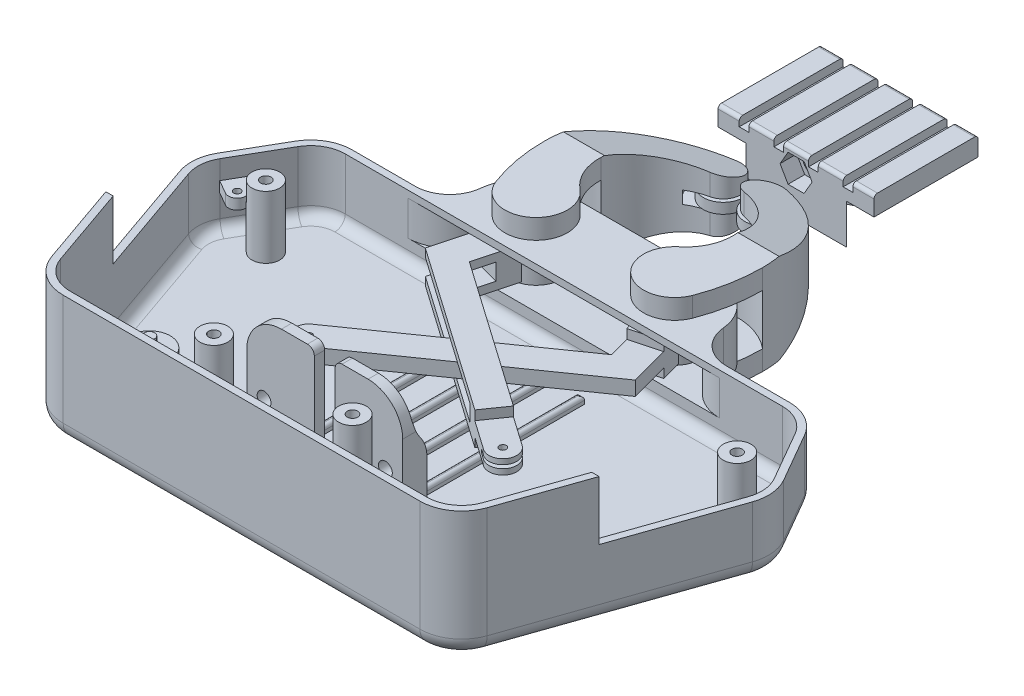
SolidWorks part; units mm, degrees
ref_plane "Front Plane" through (0, 0, 0) normal (0, 0, 1) x (1, 0, 0)
ref_plane "Top Plane" through (0, 0, 0) normal (0, 1, 0) x (1, 0, 0)
ref_plane "Right Plane" through (0, 0, 0) normal (1, 0, 0) x (0, 0, -1)
sketch "Sketch1" plane through (0, 0, 0) normal (0, 1, 0) x (1, 0, 0)
  line L0 (-70, -55) -> (-35, -55)
  line L1 (70, -55) -> (84.4338, -80)
  line L2 (84.4338, -80) -> (60, -150)
  line L3 (60, -150) -> (-60, -150)
  line L4 (-60, -150) -> (-84.4338, -80)
  line L5 (-84.4338, -80) -> (-70, -55)
  line L6 (-35, -55) -> (-35, -35)
  line L7 (-35, -35) -> (35, -35)
  line L8 (35, -35) -> (35, -55)
  line L9 (0, -55) -> (0, -122.8119) construction
  line L10 (35, -55) -> (70, -55)
  point P15 (0, -150)
  dimension "D1" = 25
  dimension "D2" = 140
  dimension "D3" = 70
  dimension "D4" = 120
  dimension "D5" = 70
  dimension "D6" = 55
  dimension "D7" = 120
  dimension "D8" = 20
  dimension "D9" = 70
  dimension "D10" = 35
extrude "Boss-Extrude1" add sketch "Sketch1" along normal blind 2
sketch "Sketch2" plane through (0, 2, 0) normal (0, 1, 0) x (1, 0, 0)
  line L0 (84.4338, -80) -> (70, -55) construction
  line L1 (60, -150) -> (84.4338, -80) construction
  line L2 (-60, -150) -> (60, -150) construction
  line L3 (-84.4338, -80) -> (-60, -150) construction
  line L4 (-70, -55) -> (-84.4338, -80) construction
  line L6 (84.4338, -80) -> (70, -55)
  line L7 (60, -150) -> (84.4338, -80)
  line L8 (-60, -150) -> (60, -150)
  line L9 (-84.4338, -80) -> (-60, -150)
  line L10 (-70, -55) -> (-84.4338, -80)
  line L11 (70, -55) -> (35, -55)
  line L12 (68.8453, -57) -> (33, -57)
  line L13 (-68.8453, -57) -> (-82.2434, -80.2062)
  line L14 (-82.2434, -80.2062) -> (-58.5798, -148)
  line L15 (-58.5798, -148) -> (58.5798, -148)
  line L16 (58.5798, -148) -> (82.2434, -80.2062)
  line L17 (82.2434, -80.2062) -> (68.8453, -57)
  line L18 (-35, -55) -> (-35, -35)
  line L19 (-35, -35) -> (35, -35)
  line L20 (35, -35) -> (35, -55)
  line L21 (-35, -55) -> (-70, -55)
  line L22 (-33, -57) -> (-33, -37)
  line L23 (70, -55) -> (-70, -55) construction
  line L24 (-33, -37) -> (33, -37)
  line L25 (33, -37) -> (33, -57)
  line L26 (-33, -57) -> (-68.8453, -57)
  line L28 (68.8453, -57) -> (-68.8453, -57) construction
  dimension "D1" = 2
  dimension "D2" = 2
  dimension "D3" = 2
  dimension "D4" = 2
extrude "Boss-Extrude2" add sketch "Sketch2" along normal blind 35
sketch "Sketch20" plane through (0, 0, 0) normal (0, -1, 0) x (1, 0, 0)
  line L0 (70, 55) -> (35, 55) construction
  line L1 (-35, 35) -> (35, 35)
  line L2 (-35, 35) -> (-35, 55)
  line L3 (-35, 55) -> (35, 55)
  line L4 (35, 35) -> (35, 55)
  line L5 (35, 55) -> (35, 35) construction
  line L6 (35, 35) -> (-35, 35) construction
  line L7 (-35, 35) -> (-35, 55) construction
extrude "Cut-Extrude7" cut sketch "Sketch20" against normal blind 8
sketch "Sketch21" plane through (0, 8, 0) normal (0, -1, 0) x (1, 0, 0)
  line L1 (-35, 35) -> (35, 35)
  line L2 (-35, 35) -> (-35, 55)
  line L3 (-35, 55) -> (35, 55)
  line L4 (35, 35) -> (35, 55)
extrude "Boss-Extrude12" add sketch "Sketch21" along normal blind 2
sketch "Sketch22" plane through (0, 0, 55) normal (0, 0, 1) x (1, 0, 0)
  line L1 (-33, 2) -> (33, 2)
  line L2 (-33, 2) -> (-33, 8)
  line L3 (-33, 8) -> (33, 8)
  line L4 (33, 2) -> (33, 8)
extrude "Boss-Extrude13" add sketch "Sketch22" along normal blind 2
sketch "Sketch23" plane through (0, 37, 0) normal (0, 1, 0) x (1, 0, 0)
  line L0 (35, -35) -> (-35, -35) construction
  line L1 (-35, -57) -> (35, -57)
  line L2 (-35, -57) -> (-35, -35)
  line L3 (-35, -35) -> (35, -35)
  line L4 (35, -57) -> (35, -35)
  line L5 (-35, -35) -> (-35, -55) construction
  line L6 (35, -55) -> (35, -35) construction
  line L7 (33, -57) -> (-33, -57) construction
extrude "Cut-Extrude8" cut sketch "Sketch23" against normal offset from surface (19 mm away) 12 up to face at (0, 6, 45)
sketch "Sketch24" plane through (0, 18, 0) normal (0, 1, 0) x (1, 0, 0)
  line L1 (-35, -35) -> (35, -35)
  line L2 (-35, -35) -> (-35, -57)
  line L3 (-35, -57) -> (35, -57)
  line L4 (35, -35) -> (35, -57)
  line L5 (-35, -35) -> (35, -35) construction
  line L6 (-35, -55) -> (-35, -35) construction
  line L8 (35, -35) -> (35, -55) construction
  line L9 (-35, -57) -> (-68.8453, -57) construction
extrude "Boss-Extrude16" add sketch "Sketch24" along normal blind 2
sketch "Sketch26" plane through (0, 0, 0) normal (0, -1, 0) x (1, 0, 0)
  line L0 (0, 35) -> (0, 168.1743) construction
  line L1 (-35, 35) -> (35, 35) construction
  circle A0 centre (20, 45) radius 7.5
  circle A1 centre (-20, 45) radius 7.5
  dimension "D1" = 15
  dimension "D2" = 10
  dimension "D3" = 20
extrude "Cut-Extrude9" cut sketch "Sketch26" against normal through all
sketch "Sketch27" plane through (0, 8, 0) normal (0, 1, 0) x (1, 0, 0)
  line L0 (-29.5, -45) -> (-27.5, -45)
  line L1 (-10.5, -45) -> (-12.5, -45)
  line L2 (0, -35) -> (0, -72.4721) construction
  line L3 (35, -35) -> (-35, -35) construction
  line L4 (29.5, -45) -> (27.5, -45)
  line L5 (10.5, -45) -> (12.5, -45)
  arc A0 (-27.5, -45) -> (-12.5, -45) centre (-20, -45) cw
  circle A1 centre (-20, -45) radius 7.5 construction
  arc A2 (-10.5, -45) -> (-29.5, -45) centre (-20, -45) ccw
  arc A3 (27.5, -45) -> (12.5, -45) centre (20, -45) ccw
  arc A4 (10.5, -45) -> (29.5, -45) centre (20, -45) cw
  dimension "D1" = 9.5
extrude "Boss-Extrude18" add sketch "Sketch27" along normal up to surface (10 mm away) up to face at (20, 18, 52.5)
sketch "Sketch25" plane through (0, 20, 0) normal (0, 1, 0) x (1, 0, 0)
  line L0 (35, -57) -> (35, -55) construction
  line L1 (-35, -57) -> (35, -57)
  line L2 (-35, -57) -> (-35, -55)
  line L3 (-35, -55) -> (35, -55)
  line L4 (35, -57) -> (35, -55)
  line L5 (-35, -57) -> (35, -57) construction
  line L6 (-35, -55) -> (-35, -57) construction
  line L7 (-35, -55) -> (-70, -55) construction
extrude "Boss-Extrude17" add sketch "Sketch25" along normal up to surface (17 mm away) up to face at (0, 37, 85.2758)
fillet "Fillet8" radius 10 2 edges at (-33, 13, 37) (33, 13, 37)
fillet "Fillet9" radius 12 2 edges at (35, 13, 35) (-35, 13, 35)
sketch "Sketch32" plane through (0, 6, 0) normal (0, -1, 0) x (1, 0, 0)
  circle A0 centre (-20, 45) radius 7.35
  circle A1 centre (-20, 45) radius 7.5 construction
  dimension "D1" = 14.7
extrude "Boss-Extrude22" add sketch "Sketch32" against normal offset from surface (14.6 mm away) 0.3 from offset 0.3 separate body up to face at (0, 20, 44.8382) offset beyond the face yes
ref_plane "Plane6" through (0, 13, 0) normal (0, -1, 0) x (-1, 0, 0)
sketch "Sketch34" plane through (0, 13, 0) normal (0, -1, 0) x (-1, 0, 0)
  line L0 (0, -55) -> (0, -6.1056) construction
  line L1 (-35, -55) -> (35, -55) construction
  circle A0 centre (6, -5) radius 6
  circle A1 centre (20, -45) radius 7.5 construction
  circle A2 centre (20, -45) radius 7.5 construction
  circle A3 centre (6, -5) radius 2.8
  dimension "D1" = 12
  dimension "D3" = 5.6
  dimension "D2" = 40
extrude "Boss-Extrude23" add sketch "Sketch34" along normal mid plane 3 separate body
sketch "Sketch36" plane through (0, 13, 0) normal (0, -1, 0) x (-1, 0, 0)
  circle A0 centre (6, -5) radius 2.5
  dimension "D1" = 5
extrude "Boss-Extrude24" add sketch "Sketch36" along normal mid plane 3.6 separate body
sketch "Sketch37" plane through (0, 11.2, 0) normal (0, -1, 0) x (1, 0, 0)
  line L0 (-1.0405, 27.7489) -> (-20, 45) construction
  line L1 (-6, 5) -> (-1.0405, 27.7489) construction
  line L2 (0.4875, 31.2396) -> (-20, 45) construction
  line L3 (0.4875, 31.2396) -> (-6, 5) construction
  arc A0 (-4.935, 9.8853) -> (-7.2001, 0.1462) centre (-6, 5) cw
  circle A1 centre (-20, 45) radius 7.35 construction
  arc A2 (-14.5636, 40.0535) -> (-26.1015, 49.0981) centre (-20, 45) ccw construction
  arc A3 (-4.935, 9.8853) -> (-14.5636, 40.0535) centre (-1.0405, 27.7489) cw construction
  arc A4 (-26.1015, 49.0981) -> (-7.2001, 0.1462) centre (0.4875, 31.2396) ccw construction
  arc A5 (-31.5421, 31.1877) -> (-19.3089, 27.0133) centre (-20, 45) ccw
  arc A6 (-31.5421, 31.1877) -> (-7.2001, 0.1462) centre (0.4875, 31.2396) ccw
  arc A7 (-19.3089, 27.0133) -> (-4.935, 9.8853) centre (-1.0405, 27.7489) ccw
  dimension "D1" = 5
  dimension "D4" = 18
  dimension "D2" = 60
  dimension "D3" = 70
extrude "Boss-Extrude25" add sketch "Sketch37" along normal up to surface (11.2 mm away) up to face at (0, 0, 95)
sketch "Sketch39" plane through (0, 5.7, 0) normal (0, -1, 0) x (1, 0, 0)
  arc A0 (-14.3353, 38.0064) -> (-28.4038, 48.2211) centre (-20, 45) ccw
  arc A1 (-31.5421, 31.1877) -> (-19.3089, 27.0133) centre (-20, 45) ccw construction
  arc A2 (-31.5421, 31.1877) -> (-19.3089, 27.0133) centre (-20, 45) ccw
  arc A3 (-31.5421, 31.1877) -> (-28.4038, 48.2211) centre (15.8356, 31.2644) cw
  arc A4 (-31.5421, 31.1877) -> (-7.2001, 0.1462) centre (0.4875, 31.2396) ccw construction
  arc A5 (-19.3089, 27.0133) -> (-14.3353, 38.0064) centre (-5.8694, 27.5545) cw
  arc A6 (-19.3089, 27.0133) -> (-4.935, 9.8853) centre (-1.0405, 27.7489) ccw construction
  dimension "D1" = 18
extrude "Boss-Extrude26" add sketch "Sketch39" along direction (0, -1, 0) on the side of the normal up to surface (5.7 mm away) up to face at (-16.6764, 0, 14.8256)
sketch "Sketch40" plane through (0, 20.3, 0) normal (0, 1, 0) x (1, 0, 0)
  arc A1 (-28.4038, -48.2211) -> (-14.3353, -38.0064) centre (-20, -45) ccw construction
  arc A2 (-19.3089, -27.0133) -> (-14.3353, -38.0064) centre (-5.8694, -27.5545) ccw construction
  arc A3 (-19.3089, -27.0133) -> (-31.5421, -31.1877) centre (-20, -45) ccw construction
  arc A4 (-31.5421, -31.1877) -> (-28.4038, -48.2211) centre (15.8356, -31.2644) ccw construction
  arc A5 (-28.4038, -48.2211) -> (-14.3353, -38.0064) centre (-20, -45) ccw
  arc A6 (-19.3089, -27.0133) -> (-14.3353, -38.0064) centre (-5.8694, -27.5545) ccw
  arc A7 (-19.3089, -27.0133) -> (-31.5421, -31.1877) centre (-20, -45) ccw
  arc A8 (-31.5421, -31.1877) -> (-28.4038, -48.2211) centre (15.8356, -31.2644) ccw
extrude "Boss-Extrude27" add sketch "Sketch40" along normal blind 5.7
sketch "Sketch41" plane through (0, 14.8, 0) normal (0, 1, 0) x (1, 0, 0)
  arc A0 (-4.935, -9.8853) -> (-7.2001, -0.1462) centre (-6, -5) ccw construction
  arc A1 (-19.3089, -27.0133) -> (-31.5421, -31.1877) centre (-20, -45) ccw construction
  arc A2 (-4.935, -9.8853) -> (-19.3089, -27.0133) centre (-1.0405, -27.7489) ccw construction
  arc A3 (-7.2001, -0.1462) -> (-31.5421, -31.1877) centre (0.4875, -31.2396) ccw construction
  arc A4 (-4.935, -9.8853) -> (-7.2001, -0.1462) centre (-6, -5) ccw
  arc A5 (-19.3089, -27.0133) -> (-31.5421, -31.1877) centre (-20, -45) ccw
  arc A6 (-4.935, -9.8853) -> (-19.3089, -27.0133) centre (-1.0405, -27.7489) ccw
  arc A7 (-7.2001, -0.1462) -> (-31.5421, -31.1877) centre (0.4875, -31.2396) ccw
extrude "Boss-Extrude28" add sketch "Sketch41" along normal up to surface (11.2 mm away) up to face at (-22.3518, 26, 38.2988)
sketch "Sketch43" plane through (0, 11.2, 0) normal (0, 1, 0) x (1, 0, 0)
  arc A1 (-4.935, -9.8853) -> (-19.3089, -27.0133) centre (-1.0405, -27.7489) ccw construction
  arc A3 (-19.3089, -27.0133) -> (-31.5421, -31.1877) centre (-20, -45) ccw construction
  arc A5 (-10.5871, -12.156) -> (-19.3089, -27.0133) centre (-1.0405, -27.7489) ccw
  arc A6 (-7.2001, -0.1462) -> (-31.5421, -31.1877) centre (0.4875, -31.2396) ccw construction
  arc A7 (-19.3089, -27.0133) -> (-31.5421, -31.1877) centre (-20, -45) ccw
  arc A8 (-14.2045, -2.7783) -> (-10.5871, -12.156) centre (-6, -5) ccw
  arc A9 (-14.2045, -2.7783) -> (-31.5421, -31.1877) centre (0.4875, -31.2396) ccw
  arc A13 (-4.935, -9.8853) -> (-7.2001, -0.1462) centre (-6, -5) ccw construction
  dimension "D1" = 17
extrude "Boss-Extrude29" add sketch "Sketch43" along normal up to surface (3.6 mm away) up to face at (-6, 14.8, 2.5)
sketch "Sketch44" plane through (0, 0, 0) normal (1, 0, 0) x (0, 0, -1)
  line L0 (0, 17.8) -> (-26.0133, 26)
  line L1 (-26.0133, 26) -> (0, 26)
  line L4 (0, 14.8) -> (0, 26) construction
  line L5 (-9.8853, 26) -> (-27.0133, 26) construction
  line L6 (0, 17.8) -> (0, 26)
  line L7 (-15.422, 13) -> (22.0298, 13) construction
  line L8 (-94.4278, 13) -> (94.4278, 13) construction
  line L9 (0, 8.2) -> (-26.0133, 0)
  line L10 (-26.0133, 0) -> (0, 0)
  line L11 (0, 8.2) -> (0, 0)
  dimension "D1" = 1
  dimension "D2" = 3
extrude "Cut-Extrude10" cut sketch "Sketch44" against normal up to surface (31.1129 mm away) up to face at (-19.4224, 13, 12.2098)
ref_plane "Plane2" through (0, 0, 0) normal (1, 0, 0) x (0, 0, -1)
ref_plane "Plane3" through (0, 0, 126) normal (0, 0, -1) x (-1, 0, 0)
sketch "Sketch45" plane through (0, 13, 0) normal (0, -1, 0) x (-1, 0, 0)
  circle A0 centre (6, -5) radius 6 construction
  circle A1 centre (6, -5) radius 6
  circle A2 centre (6, -5) radius 5.75
  dimension "D1" = 11.5
extrude "Cut-Extrude11" cut sketch "Sketch45" along normal up to surface (1.5 mm away) from surface up to face at (-6, 11.5, -1) starting at face at (-6, 14.5, -1)
mirror "Mirror8" about plane through (0, 0, 0) normal (1, 0, 0) of bodies 137 140
sketch "Sketch8" plane through (0, 0, 126) normal (0, 0, -1) x (-1, 0, 0)
  line L0 (-68.8453, 2) -> (68.8453, 2) construction
  line L1 (-68.8453, 2) -> (68.8453, 2) construction
  line L2 (60, 0) -> (-60, 0) construction
  line L3 (22.5, 2) -> (-22.5, 2)
  line L4 (22.5, 2) -> (22.5, 36)
  line L5 (22.5, 36) -> (-22.5, 36)
  line L6 (-22.5, 2) -> (-22.5, 36)
  line L7 (60, 0) -> (-60, 0) construction
  line L8 (0, 14.8493) -> (0, -14.8493) construction
  dimension "D1" = 34
  dimension "D2" = 45
  dimension "D3" = 22.5
extrude "Boss-Extrude5" add sketch "Sketch8" along normal blind 3
sketch "Sketch9" plane through (0, 2, 0) normal (0, 1, 0) x (1, 0, 0)
  line L1 (-22.5, -123) -> (-19.5, -123)
  line L2 (-22.5, -123) -> (-22.5, -119)
  line L3 (-22.5, -119) -> (-19.5, -119)
  line L4 (-19.5, -123) -> (-19.5, -119)
  line L5 (22.5, -123) -> (19.5, -123)
  line L6 (22.5, -123) -> (22.5, -119)
  line L7 (22.5, -119) -> (19.5, -119)
  line L8 (19.5, -123) -> (19.5, -119)
  dimension "D1" = 3
  dimension "D2" = 4
extrude "Boss-Extrude6" add sketch "Sketch9" along normal blind 20
fillet "Fillet1" radius 10 2 edges at (-21, 22, 123) (21, 22, 123)
fillet "Fillet2" radius 10 2 edges at (-21, 22, 119) (21, 22, 119)
sketch "Sketch11" plane through (0, 2, 0) normal (0, 1, 0) x (1, 0, 0)
  line L0 (-58.5798, -148) -> (58.5798, -148) construction
  circle A0 centre (-43.5798, -133) radius 3.5
  circle A1 centre (-43.5798, -133) radius 1.85
  dimension "D1" = 7
  dimension "D4" = 3.7
  dimension "D2" = 15
  dimension "D3" = 15
sketch "Sketch15" plane through (0, 0, 126) normal (0, 0, 1) x (1, 0, 0)
  line L1 (22.5, 2) -> (-22.5, 2) construction
  line L2 (22.5, 2) -> (-22.5, 2) construction
  line L3 (0, -14.8493) -> (0, 14.8493) construction
  circle A0 centre (17.5, 16) radius 2
  circle A1 centre (-17.5, 16) radius 2
  circle A3 centre (0, 8) radius 4.65
  dimension "D1" = 8
  dimension "D2" = 4
  dimension "D3" = 4
  dimension "D6" = 9.3
  dimension "D4" = 35
  dimension "D5" = 17.5
  dimension "D7" = 6
extrude "Cut-Extrude5" cut sketch "Sketch15" against normal up to surface (3 mm away) up to face at (0, 24.5, 123)
fillet "Fillet3" radius 10 8 edges at (-35, 13, 55) (35, 13, 55) (58.5798, 19.5, 148) (-58.5798, 19.5, 148) (82.2434, 19.5, 80.2062) (68.8453, 19.5, 57) (-82.2434, 19.5, 80.2062) (-68.8453, 19.5, 57)
fillet "Fillet4" radius 12 8 edges at (-60, 18.5, 150) (-84.4338, 18.5, 80) (-70, 18.5, 55) (-33, 13, 57) (33, 13, 57) (70, 18.5, 55) (60, 18.5, 150) (84.4338, 18.5, 80)
fillet "Fillet5" radius 10 2 edges at (22.5, 36, 124.5) (-22.5, 36, 124.5)
fillet "Fillet6" radius 3 12 edges at (-70.8266, 2, 112.9143) (-81.2478, 2, 80.3) (-75.842, 2, 69.1187) (-68.0718, 2, 58.3397) (0, 2, 57) (68.0718, 2, 58.3397) (75.842, 2, 69.1187) (81.2478, 2, 80.3) (70.8266, 2, 112.9143) (0, 2, 148) (-57.2685, 2, 146.1534) (57.2685, 2, 146.1534)
fillet "Fillet7" radius 5 12 edges at (69.0718, 0, 56.6077) (77.5741, 0, 68.1187) (83.2389, 0, 80.1125) (72.7148, 0, 113.5734) (58.4264, 0, 147.7841) (0, 0, 150) (-58.4264, 0, 147.7841) (-72.7148, 0, 113.5734) (-83.2389, 0, 80.1125) (-77.5741, 0, 68.1187) (-69.0718, 0, 56.6077) (0, 0, 55)
sketch "Sketch16" plane through (0, 0, 0) normal (1, 0, 0) x (0, 0, -1)
  line L0 (-83.5443, 0) -> (-140.3069, 0) construction
  line L1 (-118, 40) -> (-28, 40)
  line L2 (-118, 40) -> (-118, 20)
  line L3 (-118, 20) -> (-28, 20)
  line L4 (-28, 40) -> (-28, 20)
  line L5 (-150, 5) -> (-150, 37) construction
  dimension "D1" = 20
  dimension "D2" = 32
  dimension "D3" = 20
  dimension "D4" = 90
extrude "Cut-Extrude6" cut sketch "Sketch16" against normal through all both and the other way through all
sketch "Sketch17" plane through (0, 2, 0) normal (0, 1, 0) x (1, 0, 0)
  line L0 (0, -14.8493) -> (0, 14.8493) construction
  line L4 (-63.0718, -55) -> (-44.9089, -55) construction
  circle A2 centre (-68, -75) radius 4
  circle A4 centre (-68, -75) radius 1.5
  circle A10 centre (68, -75) radius 1.5
  circle A11 centre (68, -75) radius 4
  dimension "D7" = 8
  dimension "D9" = 3
  dimension "D4" = 20
  dimension "D5" = 68
extrude "Boss-Extrude10" add sketch "Sketch17" along normal up to surface (18 mm away) up to face at (0, 20, 71.1525)
sketch "Sketch19" plane through (0, 2, 0) normal (0, 1, 0) x (1, 0, 0)
  line L0 (0, -14.8493) -> (0, 14.8493) construction
  line L1 (-51.4786, -150) -> (51.4786, -150) construction
  circle A0 centre (-20, -138) radius 4
  circle A1 centre (-20, -138) radius 1.5
  circle A2 centre (20, -138) radius 1.5
  circle A3 centre (20, -138) radius 4
  dimension "D1" = 3
  dimension "D2" = 8
  dimension "D3" = 20
  dimension "D4" = 12
extrude "Boss-Extrude11" add sketch "Sketch19" along normal up to surface (35 mm away) up to face at (0, 37, 136.7604)
sketch "Sketch46" plane through (0, 0, 126) normal (0, 0, 1) x (1, 0, 0)
  line L0 (-3, 8) -> (-3, 36)
  line L1 (-3, 36) -> (3, 36)
  line L3 (-3, 8) -> (3, 8)
  line L5 (-12.5, 36) -> (12.5, 36) construction
  line L7 (3, 36) -> (3, 8)
  circle A0 centre (0, 8) radius 4.65 construction
  circle A1 centre (0, 8) radius 4.65 construction
  dimension "D1" = 6
extrude "Cut-Extrude12" cut sketch "Sketch46" against normal up to surface (3 mm away) up to face at (-4.65, 8, 123)
fillet "Fillet10" radius 2 2 edges at (-3, 36, 124.5) (3, 36, 124.5)
sketch "Sketch49" plane through (0, 13, 0) normal (0, -1, 0) x (-1, 0, 0)
  line L0 (20, -45) -> (6, -5) construction
  line L1 (27.0996, -43.0977) -> (32.923, -64.831) construction
  line L2 (30.3078, -66.6622) -> (-25.7197, -105.8931)
  line L3 (12.9004, -46.9023) -> (17.9052, -65.5804) construction
  line L4 (17.9052, -65.5804) -> (-30.3083, -99.3398)
  line L5 (63.0718, -57) -> (-63.0718, -57) construction
  line L6 (30.3078, -66.6622) -> (25.7352, -49.5968)
  line L7 (20.5204, -63.7492) -> (17.3316, -51.8485)
  line L8 (17.9052, -65.5804) -> (20.5204, -63.7492)
  line L9 (30.3078, -66.6622) -> (32.923, -64.831) construction
  circle A0 centre (20, -45) radius 7.35 construction
  arc A1 (17.3316, -51.8485) -> (25.7352, -49.5968) centre (20, -45) ccw
  circle A2 centre (20, -45) radius 75 construction
  arc A3 (7.2001, -0.1462) -> (4.935, -9.8853) centre (6, -5) ccw construction
  arc A4 (7.2001, -0.1462) -> (4.935, -9.8853) centre (6, -5) ccw construction
  arc A5 (-30.3083, -99.3398) -> (-25.7197, -105.8931) centre (-28.014, -102.6165) ccw
  point P15 (26.4546, -40.6906)
  point P19 (0, 0)
  point P20 (27.0996, -43.0977)
  dimension "D1" = 150
  dimension "D2" = 110
  dimension "D3" = 4
  dimension "D4" = 22.5
  dimension "D5" = 35
  dimension "D6" = 3
  dimension "D7" = 3
extrude "Boss-Extrude30" add sketch "Sketch49" along normal offset from surface 0.3 and the other way offset from surface 0.3 separate body up to face at (0, 8, 45.5486) other way up to face at (0, 18, 45.5486)
sketch "Sketch50" plane through (-41.2919, 0, 58.971) normal (-0.5736, 0, 0.8192) x (0.8192, 0, 0.5736)
  line L0 (13.4091, 8.3) -> (13.4091, 17.7) construction
  line L1 (13.4091, 15.4) -> (65.8061, 15.4)
  line L2 (13.4091, 15.4) -> (13.4091, 10.6)
  line L3 (13.4091, 10.6) -> (65.8061, 10.6)
  line L4 (65.8061, 15.4) -> (65.8061, 10.6)
  line L5 (85.8061, 8.3) -> (85.8061, 17.7) construction
  line L6 (13.4091, 15.4) -> (13.4091, 17.7) construction
  line L7 (81.8061, 17.7) -> (13.4091, 17.7) construction
  line L8 (13.4091, 10.6) -> (13.4091, 8.3) construction
  line L9 (13.4091, 8.3) -> (81.8061, 8.3) construction
  dimension "D1" = 4.8
  dimension "D2" = 0
  dimension "D3" = 20
extrude "Cut-Extrude13" cut sketch "Sketch50" against normal up to surface (8 mm away) up to face at (4.894, 13, 81.5445)
sketch "Sketch51" plane through (0, 13, 0) normal (0, -1, 0) x (-1, 0, 0)
  line L0 (30.3078, -66.6622) -> (25.7352, -49.5968) construction
  line L1 (17.3316, -51.8485) -> (20.5204, -63.7492) construction
  line L3 (-25.7197, -105.8931) -> (30.3078, -66.6622) construction
  line L6 (20.5204, -63.7492) -> (-30.3083, -99.3398) construction
  line L22 (17.3316, -51.8485) -> (20.5204, -63.7492) construction
  line L23 (20.5204, -63.7492) -> (-30.3083, -99.3398) construction
  line L24 (-25.7197, -105.8931) -> (30.3078, -66.6622) construction
  line L25 (30.3078, -66.6622) -> (25.7352, -49.5968) construction
  line L26 (0, 14.8493) -> (0, -14.8493) construction
  line L27 (-20.5204, -63.7492) -> (30.3083, -99.3398)
  line L28 (-17.3316, -51.8485) -> (-20.5204, -63.7492)
  line L29 (-30.3078, -66.6622) -> (-25.7352, -49.5968)
  line L30 (25.7197, -105.8931) -> (-30.3078, -66.6622)
  arc A0 (17.3316, -51.8485) -> (25.7352, -49.5968) centre (20, -45) ccw construction
  arc A6 (-30.3083, -99.3398) -> (-25.7197, -105.8931) centre (-28.014, -102.6165) ccw construction
  arc A10 (-30.3083, -99.3398) -> (-25.7197, -105.8931) centre (-28.014, -102.6165) ccw construction
  arc A11 (17.3316, -51.8485) -> (25.7352, -49.5968) centre (20, -45) ccw construction
  arc A12 (30.3083, -99.3398) -> (25.7197, -105.8931) centre (28.014, -102.6165) cw
  arc A13 (-17.3316, -51.8485) -> (-25.7352, -49.5968) centre (-20, -45) cw
extrude "Boss-Extrude32" add sketch "Sketch51" along normal offset from surface 0.3 and the other way offset from surface 0.4 up to face at (-9.3465, 10.6, 75.4798) other way up to face at (-9.3465, 15.4, 75.4798)
sketch "Sketch52" plane through (0, 13, 0) normal (0, -1, 0) x (-1, 0, 0)
  line L2 (-25.7352, -49.5968) -> (-30.3078, -66.6622) construction
  line L3 (-20.5204, -63.7492) -> (-17.3316, -51.8485) construction
  line L6 (-25.7352, -49.5968) -> (-27.3076, -55.4652)
  line L7 (-18.9041, -57.717) -> (-17.3316, -51.8485)
  line L9 (-18.9041, -57.717) -> (-27.3076, -55.4652)
  line L10 (63.0718, -57) -> (-63.0718, -57) construction
  arc A0 (-25.7352, -49.5968) -> (-17.3316, -51.8485) centre (-20, -45) ccw construction
  arc A1 (-25.7352, -49.5968) -> (-17.3316, -51.8485) centre (-20, -45) ccw
  circle A2 centre (-20, -45) radius 12 construction
  point P2 (-27.4936, -56.1593)
extrude "Boss-Extrude33" add sketch "Sketch52" along normal up to surface (4.7 mm away) from surface up to face at (-5.8265, 8.3, 73.4601) starting at face at (-5.8265, 17.7, 73.4601)
sketch "Sketch53" plane through (0, 17.7, 0) normal (0, 1, 0) x (1, 0, 0)
  line L0 (-20.5204, -63.7492) -> (30.3083, -99.3398) construction
  line L1 (25.7197, -105.8931) -> (-30.3078, -66.6622) construction
  line L2 (21.8792, -93.4377) -> (30.3083, -99.3398)
  line L3 (25.7197, -105.8931) -> (17.2906, -99.9909)
  line L4 (17.2906, -99.9909) -> (21.8792, -93.4377)
  arc A0 (25.7197, -105.8931) -> (30.3083, -99.3398) centre (28.014, -102.6165) ccw construction
  arc A1 (25.7197, -105.8931) -> (30.3083, -99.3398) centre (28.014, -102.6165) ccw
  point P5 (31.2906, -104.9108)
  dimension "D1" = 14
extrude "Cut-Extrude14" cut sketch "Sketch53" against normal up to surface (2.7 mm away) up to face at (6.2892, 15, 75.1868)
sketch "Sketch54" plane through (0, 8.3, 0) normal (0, -1, 0) x (1, 0, 0)
  line L0 (25.7197, 105.8931) -> (17.2906, 99.9909) construction
  line L1 (21.8792, 93.4377) -> (30.3083, 99.3398) construction
  line L2 (17.2906, 99.9909) -> (21.8792, 93.4377) construction
  line L3 (25.7197, 105.8931) -> (17.2906, 99.9909)
  line L4 (21.8792, 93.4377) -> (30.3083, 99.3398)
  line L5 (17.2906, 99.9909) -> (21.8792, 93.4377)
  arc A0 (30.3083, 99.3398) -> (25.7197, 105.8931) centre (28.014, 102.6165) ccw construction
  arc A1 (30.3083, 99.3398) -> (25.7197, 105.8931) centre (28.014, 102.6165) ccw
extrude "Cut-Extrude15" cut sketch "Sketch54" against normal up to surface (2.6 mm away) up to face at (6.2892, 10.9, 75.1868)
sketch "Sketch55" plane through (0, 15, 0) normal (0, 1, 0) x (1, 0, 0)
  arc A0 (-30.3083, -99.3398) -> (-25.7197, -105.8931) centre (-28.014, -102.6165) ccw construction
  arc A1 (25.7197, -105.8931) -> (30.3083, -99.3398) centre (28.014, -102.6165) ccw construction
  arc A2 (-30.3083, -99.3398) -> (-25.7197, -105.8931) centre (-28.014, -102.6165) ccw construction
  arc A3 (25.7197, -105.8931) -> (30.3083, -99.3398) centre (28.014, -102.6165) ccw construction
  circle A4 centre (-28.014, -102.6165) radius 1
  circle A5 centre (28.014, -102.6165) radius 1
  dimension "D1" = 2
  dimension "D2" = 2
extrude "Cut-Extrude16" cut sketch "Sketch55" against normal up to surface (4.1 mm away) up to face at (6.2892, 10.9, 75.1868)
sketch "Sketch56" plane through (0, 2, 0) normal (0, 1, 0) x (1, 0, 0)
  line L0 (0, -14.8493) -> (0, 14.8493) construction
  line L1 (-16, -119) -> (-14, -119)
  line L2 (-16, -119) -> (-16, -67)
  line L3 (-16, -67) -> (-14, -67)
  line L4 (-14, -119) -> (-14, -67)
  line L5 (-6, -119) -> (-4, -119)
  line L6 (-6, -119) -> (-6, -67)
  line L7 (-6, -67) -> (-4, -67)
  line L8 (-4, -119) -> (-4, -67)
  line L9 (-63.0718, -57) -> (63.0718, -57) construction
  point P10 (-7.2699, -121.6995)
  point P11 (0, 0)
  point P12 (0, 0)
  point P16 (0, 0)
  dimension "D1" = 4
  dimension "D2" = 8
  dimension "D3" = 10
  dimension "D4" = 2
extrude "Boss-Extrude34" add sketch "Sketch56" along normal blind 2
fillet "Fillet11" radius 1 8 edges at (-15, 4, 119) (-5, 4, 119) (-5, 4, 67) (-15, 4, 67) (-4, 4, 93) (-6, 4, 93) (-14, 4, 93) (-16, 4, 93)
mirror "Mirror11" about plane through (0, 0, 0) normal (1, 0, 0) of "Fillet11", "Boss-Extrude34"
sketch "Sketch58" plane through (0, 2, 0) normal (0, 1, 0) x (1, 0, 0)
  line L0 (-22.5, -119) -> (-22.5, -126) construction
  line L1 (-22.5, 40) -> (22.5, 40)
  line L2 (-22.5, 40) -> (-22.5, 10)
  line L3 (-22.5, 10) -> (22.5, 10)
  line L4 (22.5, 40) -> (22.5, 10)
  line L5 (22.5, -119) -> (22.5, -126) construction
  line L6 (23, -35) -> (-23, -35) construction
  dimension "D1" = 30
  dimension "D2" = 45
extrude "Boss-Extrude35" add sketch "Sketch58" along normal offset from surface (17 mm away) 1 separate body up to face at (0, 20, 71.1525)
sketch "Sketch60" plane through (0, 19, 0) normal (0, 1, 0) x (1, 0, 0)
  line L0 (-14, -119) -> (-14, -67) construction
  line L1 (-4, -119) -> (-4, -67) construction
  line L2 (6, -67) -> (6, -119) construction
  line L3 (16, -67) -> (16, -119) construction
  line L4 (14, -119) -> (14, -67) construction
  line L5 (4, -119) -> (4, -67) construction
  line L6 (-6, -67) -> (-6, -119) construction
  line L7 (-16, -67) -> (-16, -119) construction
  line L8 (-14, -119) -> (-14, -67) construction
  line L9 (-4, -119) -> (-4, -67) construction
  line L10 (6, -67) -> (6, -119) construction
  line L11 (16, -46.9969) -> (16, -119) construction
  line L12 (14, -119) -> (14, -67) construction
  line L13 (4, -119) -> (4, -67) construction
  line L14 (-6, -67) -> (-6, -119) construction
  line L15 (-16, -67) -> (-16, -119) construction
  line L16 (16, 40) -> (16, 10) construction
  line L17 (22.5, 40) -> (-22.5, 40) construction
  line L18 (14, 10) -> (14, 40) construction
  line L19 (6, 10) -> (6, 40) construction
  line L20 (4, 10) -> (4, 40) construction
  line L21 (-4, 10) -> (-4, 40) construction
  line L22 (-6, 10) -> (-6, 40) construction
  line L23 (-14, 10) -> (-14, 40) construction
  line L24 (-16, 10) -> (-16, 40) construction
  line L27 (-22.5, 10) -> (22.5, 10) construction
  line L28 (-16, 40) -> (-14, 40) construction
  line L29 (-6, 40) -> (-4, 40) construction
  line L30 (4, 40) -> (6, 40) construction
  line L31 (14, 40) -> (16, 40) construction
  line L32 (16, 10) -> (14, 10) construction
  line L33 (6, 10) -> (4, 10) construction
  line L34 (-4, 10) -> (-6, 10) construction
  line L35 (-14, 10) -> (-16, 10) construction
  line L36 (16.4, 40.4) -> (16.4, 9.6)
  line L37 (16.4, 9.6) -> (13.6, 9.6)
  line L38 (13.6, 9.6) -> (13.6, 40.4)
  line L39 (13.6, 40.4) -> (16.4, 40.4)
  line L40 (6.4, 9.6) -> (6.4, 40.4)
  line L41 (3.6, 40.4) -> (6.4, 40.4)
  line L42 (3.6, 9.6) -> (3.6, 40.4)
  line L43 (6.4, 9.6) -> (3.6, 9.6)
  line L44 (-3.6, 9.6) -> (-3.6, 40.4)
  line L45 (-6.4, 40.4) -> (-3.6, 40.4)
  line L46 (-6.4, 9.6) -> (-6.4, 40.4)
  line L47 (-3.6, 9.6) -> (-6.4, 9.6)
  line L48 (-13.6, 9.6) -> (-13.6, 40.4)
  line L49 (-16.4, 40.4) -> (-13.6, 40.4)
  line L50 (-16.4, 9.6) -> (-16.4, 40.4)
  line L51 (-13.6, 9.6) -> (-16.4, 9.6)
  dimension "D1" = 0.4
extrude "Cut-Extrude17" cut sketch "Sketch60" against normal blind 2.4
fillet "Fillet12" radius 1 10 edges at (-19.45, 19, -10) (-10, 19, -10) (0, 19, -10) (10, 19, -10) (19.45, 19, -10) (19.45, 19, -40) (10, 19, -40) (0, 19, -40) (-10, 19, -40) (-19.45, 19, -40)
sketch "Sketch61" plane through (0, 2, 0) normal (0, -1, 0) x (1, 0, 0)
  line L7 (-22.5, -10) -> (-22.5, -40)
  line L8 (-22.5, -40) -> (22.5, -40)
  line L9 (22.5, -40) -> (22.5, -10)
  line L10 (22.5, -10) -> (14.5, -10)
  line L11 (-22.5, -10) -> (22.5, -10) construction
  line L12 (14.5, -10) -> (6, -18)
  line L13 (6, -18) -> (-6, -18)
  line L15 (-6, -18) -> (-14.5, -10)
  line L16 (-14.5, -10) -> (-22.5, -10)
  dimension "D1" = 8
  dimension "D2" = 8
  dimension "D3" = 8
  dimension "D4" = 12
extrude "Cut-Extrude18" cut sketch "Sketch61" against normal offset from surface (11.5 mm away) 5.5 contours L13 L15 L16 L7 L8 L9 L10 L12 up to face at (-19.45, 19, -25)
sketch "Sketch62" plane through (0, 13.5, 0) normal (0, -1, 0) x (1, 0, 0)
  line L0 (6, -18) -> (-6, -18) construction
  line L1 (0, -18) -> (0, -71.4655) construction
  line L5 (-22.5, -40) -> (22.5, -40) construction
  circle A2 centre (0, -30) radius 10
  point P1 (0, 0)
  dimension "D1" = 20
extrude "Boss-Extrude38" add sketch "Sketch62" along normal up to surface (11.5 mm away) up to face at (0, 2, -14)
sketch "Sketch63" plane through (0, 0, -10) normal (0, 0, 1) x (1, 0, 0)
  line L0 (0, -14.8493) -> (0, 14.8493) construction
  line L1 (-3.6, 19) -> (3.6, 19) construction
  circle A0 centre (0, 13.3) radius 2.9
  point P6 (0, 0)
  dimension "D1" = 5.8
  dimension "D2" = 5.7
extrude "Cut-Extrude19" cut sketch "Sketch63" against normal up to surface (30 mm away) up to face at (0, 16.8238, -40)
sketch "Sketch66" plane through (0, 0, -10) normal (0, 0, 1) x (1, 0, 0)
  line L0 (-3.6, 19) -> (3.6, 19) construction
  line L1 (2.3094, 9.3) -> (4.6188, 13.3)
  line L2 (4.6188, 13.3) -> (2.3094, 17.3)
  line L3 (2.3094, 17.3) -> (-2.3094, 17.3)
  line L4 (-2.3094, 17.3) -> (-4.6188, 13.3)
  line L5 (-4.6188, 13.3) -> (-2.3094, 9.3)
  line L6 (-2.3094, 9.3) -> (2.3094, 9.3)
  circle A0 centre (0, 13.3) radius 4 construction
  point P1 (2.517, 17.1727)
  dimension "D1" = 8
extrude "Cut-Extrude20" cut sketch "Sketch66" against normal blind 4.8
sketch "Sketch67" plane through (-11.612, 0, -3.1114) normal (-0.9659, 0, -0.2588) x (-0.2588, 0, 0.9659)
  line L1 (72.235, 15.4) -> (60.645, 15.4)
  line L2 (72.235, 15.4) -> (72.235, 10.6)
  line L3 (72.235, 10.6) -> (60.645, 10.6)
  line L4 (60.645, 15.4) -> (60.645, 10.6)
  point P5 (0, 0)
  dimension "D1" = 11.59
extrude "Cut-Extrude21" cut sketch "Sketch67" against normal up to surface (8.7 mm away) up to face at (-19.4575, 13, 59.7823)
sketch "Sketch68" plane through (0, 2, 0) normal (0, 1, 0) x (1, 0, 0)
  line L2 (-7.5, -126) -> (-7.5, -147)
  line L3 (-7.5, -147) -> (7.5, -147)
  line L4 (7.5, -126) -> (7.5, -147)
  line L6 (-7.5, -126) -> (7.5, -126)
  line L7 (22.5, -126) -> (-22.5, -126) construction
  line L8 (0, -14.8493) -> (0, 14.8493) construction
  dimension "D1" = 21
  dimension "D2" = 15
  dimension "D3" = 7.5
extrude "Cut-Extrude22" cut sketch "Sketch68" along normal blind 5 from offset 1 offset against normal yes
extrude "Boss-Extrude39" add sketch "Sketch11" along normal blind 2
sketch "Sketch70" plane through (0, 2, 0) normal (0, 1, 0) x (1, 0, 0)
  circle A0 centre (-43.5798, -133) radius 1.5
  dimension "D1" = 3
extrude "Boss-Extrude41" add sketch "Sketch70" along normal blind 20 from offset 0.3 separate body
sketch "Sketch71" plane through (0, 4, 0) normal (0, 1, 0) x (1, 0, 0)
  circle A0 centre (-43.5798, -133) radius 3
  dimension "D1" = 6
extrude "Boss-Extrude42" add sketch "Sketch71" along normal blind 1 from offset 2
chamfer "Chamfer2" distance 1.5 angle 45 1 edges at (-43.5798, 6, 134.5)
sketch "Sketch72" plane through (0, 7, 0) normal (0, 1, 0) x (1, 0, 0)
  circle A0 centre (-43.5798, -133) radius 1.9
  circle A1 centre (-43.5798, -133) radius 11
  dimension "D1" = 22
  dimension "D2" = 3.8
extrude "Boss-Extrude43" add sketch "Sketch72" along normal blind 1 from offset 0.3 separate body
sketch "Sketch73" plane through (0, 8.3, 0) normal (0, 1, 0) x (1, 0, 0)
  circle A0 centre (-43.5798, -133) radius 3
  circle A1 centre (-43.5798, -133) radius 1.85
  dimension "D1" = 6
  dimension "D2" = 3.7
extrude "Boss-Extrude44" add sketch "Sketch73" along normal up to surface (6.7 mm away) from offset 0.3 up to face at (-28.014, 15, 103.6165)
sketch "Sketch74" plane through (0, 2, 0) normal (0, 1, 0) x (1, 0, 0)
  line L0 (-45.5853, -122.6903) -> (-54.0726, -132.5374) construction
  line L1 (-43.5798, -133) -> (-49.8289, -127.6138) construction
  line L2 (-77.9008, -83.5443) -> (-58.0876, -140.3069) construction
  circle A0 centre (-43.5798, -133) radius 8.25 construction
  circle A1 centre (-43.5798, -133) radius 11 construction
  circle A4 centre (-54.0726, -132.5374) radius 1.5
  circle A5 centre (-45.5853, -122.6903) radius 1.5
  dimension "D1" = 2.75
  dimension "D2" = 3
  dimension "D3" = 13
  dimension "D4" = 30
extrude "Boss-Extrude45" add sketch "Sketch74" along normal blind 4
sketch "Sketch75" plane through (0, 15, 0) normal (0, 1, 0) x (1, 0, 0)
  line L0 (-49.5798, -148) -> (-49.5798, -133)
  line L1 (-37.5798, -148) -> (-37.5798, -133)
  line L2 (-51.4786, -148) -> (51.4786, -148) construction
  line L3 (-49.5798, -148) -> (-37.5798, -148)
  circle A0 centre (-43.5798, -133) radius 1.85
  arc A1 (-37.5798, -133) -> (-49.5798, -133) centre (-43.5798, -133) ccw
  dimension "D1" = 3.7
  dimension "D2" = 6
extrude "Boss-Extrude46" add sketch "Sketch75" along normal blind 4 from offset 0.3
sketch "Sketch76" plane through (0, 13, 0) normal (0, -1, 0) x (-1, 0, 0)
  circle A0 centre (43.5798, -133) radius 3 construction
  circle A1 centre (43.5798, -133) radius 3
  circle A2 centre (43.5798, -133) radius 2.5
  dimension "D1" = 5
extrude "Cut-Extrude23" cut sketch "Sketch76" against normal mid plane 1.5
sketch "Sketch77" plane through (0, 13, 0) normal (0, -1, 0) x (-1, 0, 0)
  circle A0 centre (28.014, -102.6165) radius 4.75
  dimension "D1" = 9.5
extrude "Cut-Extrude24" cut sketch "Sketch77" against normal mid plane 1
sketch "Sketch78" plane through (0, 13, 0) normal (0, -1, 0) x (-1, 0, 0)
  circle A0 centre (-28.014, -102.6165) radius 4.75
  dimension "D1" = 9.5
extrude "Cut-Extrude25" cut sketch "Sketch78" against normal mid plane 1
sketch "Sketch79" plane through (0, 13, 0) normal (0, -1, 0) x (-1, 0, 0)
  line L0 (79.9971, -76.3156) -> (75.842, -69.1187)
  line L1 (79.952, -76.2375) -> (71.7321, -62) construction
  line L2 (75.842, -69.1187) -> (72.6354, -75.2405)
  line L3 (79.9971, -76.3156) -> (76.1, -78.5656)
  arc A0 (72.6354, -75.2405) -> (76.1, -78.5656) centre (74.85, -76.4005) ccw
  circle A1 centre (74.85, -76.4005) radius 1
  dimension "D1" = 2
  dimension "D4" = 2.5
  dimension "D2" = 4.5
  dimension "D3" = 6.1218
extrude "Boss-Extrude47" add sketch "Sketch79" along normal mid plane 3
